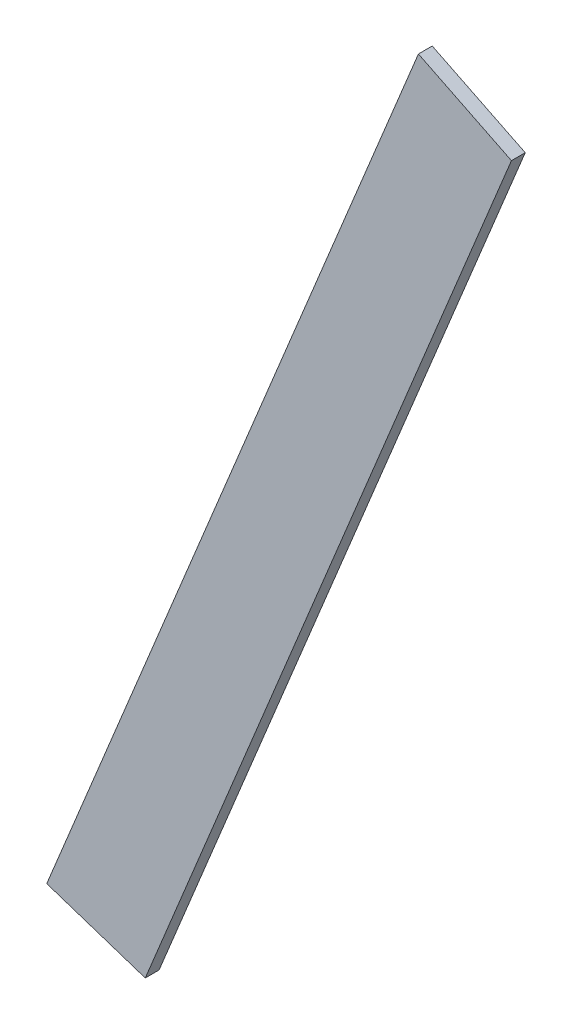
SolidWorks part; units mm, degrees
ref_plane "Front Plane" through (0, 0, 0) normal (0, 0, 1) x (1, 0, 0)
ref_plane "Top Plane" through (0, 0, 0) normal (0, 1, 0) x (1, 0, 0)
ref_plane "Right Plane" through (0, 0, 0) normal (1, 0, 0) x (0, 0, -1)
sketch "Sketch1" plane through (0, 0, 0) normal (0, 0, 1) x (1, 0, 0)
  line L0 (31.68, -12.0736) -> (17.3987, -7.3626)
  line L2 (17.3987, -7.3626) -> (71.2824, 123.7441)
  line L4 (31.68, -12.0736) -> (84.7662, 117.0927)
  line L5 (84.7662, 117.0927) -> (71.2824, 123.7441)
  line L6 (146.0308, 86.8715) -> (-33.3335, 175.3501) construction
  line L7 (-93.1797, 29.1149) -> (96.7529, -33.5399) construction
  dimension "D1" = 15
extrude "Boss-Extrude1" add sketch "Sketch1" along normal blind 2
ref_plane "Plane1" through (24.4102, -10.0324, 0) normal (0.9249, -0.3801, 0) x (0, 0, -1)
